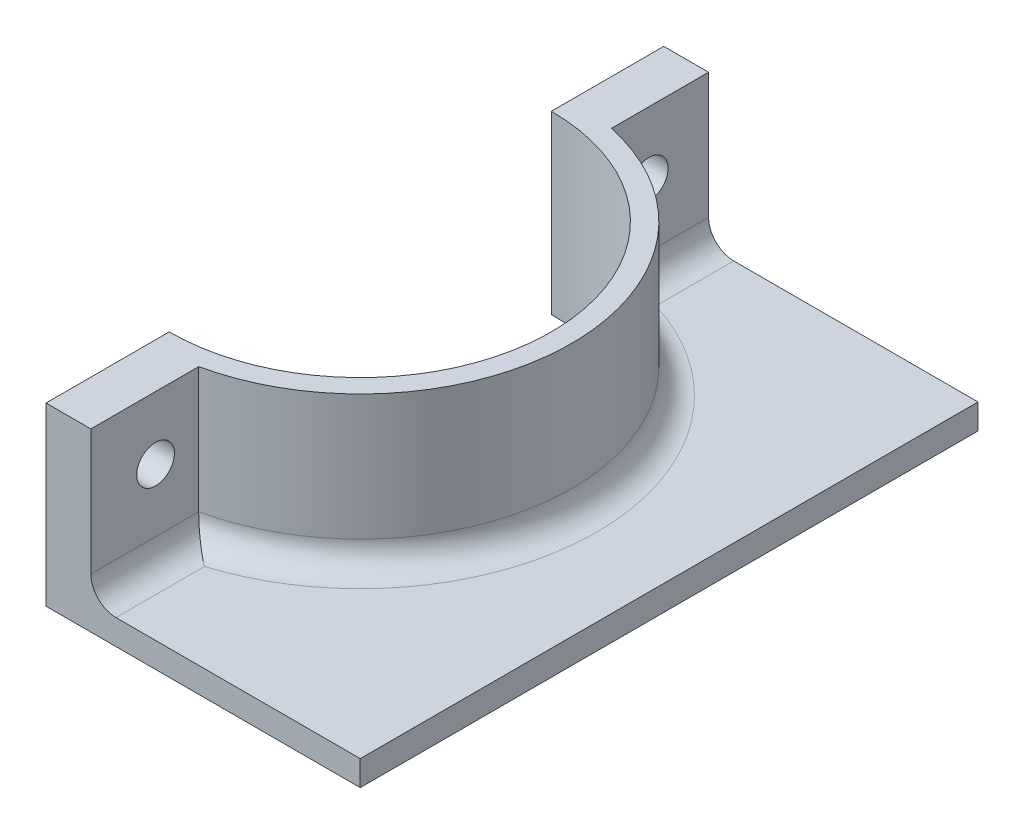
SolidWorks part; units mm, degrees
ref_plane "Front Plane" through (0, 0, 0) normal (0, 0, 1) x (1, 0, 0)
ref_plane "Top Plane" through (0, 0, 0) normal (0, 1, 0) x (1, 0, 0)
ref_plane "Right Plane" through (0, 0, 0) normal (1, 0, 0) x (0, 0, -1)
sketch "Sketch3" plane through (0, 0, 0) normal (0, 1, 0) x (1, 0, 0)
  line L0 (0, 0) -> (0, 62.4162)
  line L1 (0, 62.4162) -> (57.15, 62.4162)
  line L2 (57.15, 62.4162) -> (57.15, 0)
  line L3 (57.15, 0) -> (0, 0)
  line L4 (25.4, 62.4162) -> (25.4, 0)
  line L7 (20.8702, 62.4162) -> (20.8702, 52.5996)
  line L8 (29.9298, 62.4162) -> (29.9298, 52.5996)
  line L9 (20.8702, 0) -> (20.8702, 10.9004)
  line L10 (29.9298, 0) -> (29.9298, 10.9004)
  circle A0 centre (25.4, 31.75) radius 19.304
  arc A2 (20.8702, 52.5996) -> (20.8702, 10.9004) centre (25.4, 31.75) ccw
  arc A3 (29.9298, 10.9004) -> (29.9298, 52.5996) centre (25.4, 31.75) ccw
  point P9 (0, 0)
sketch "Sketch5" plane through (0, 0, 0) normal (1, 0, 0) x (0, 0, -1)
  circle A0 centre (6.5405, 11.43) radius 1.905
  circle A1 centre (56.4176, 11.43) radius 1.905
  point P2 (0, 0)
  point P3 (0, 0)
  point P4 (0, 0)
  point P5 (0, 0)
extrude "Boss-Extrude12" add sketch "Sketch3" along normal blind 17.78 contours L10 A3 L8 L1 L4 A0 L3 region at (26.0596, 0, -6.223)
extrude "Boss-Extrude13" add sketch "Sketch3<16>" along normal blind 2.54 contours A3 L10 L3 L2 L1 L8 region at (30.6108, 0, -5.4502)
sketch "Sketch3<16>" plane through (0, 0, 0) normal (0, 1, 0) x (1, 0, 0) same geometry as "Sketch3"
fillet "Fillet2" radius 2.54 3 edges at (29.9298, 2.54, -57.5079) (46.736, 2.54, -31.75) (29.9298, 2.54, -5.4502)
extrude "Cut-Extrude1" cut sketch "Sketch5" against normal through all both and the other way through all
